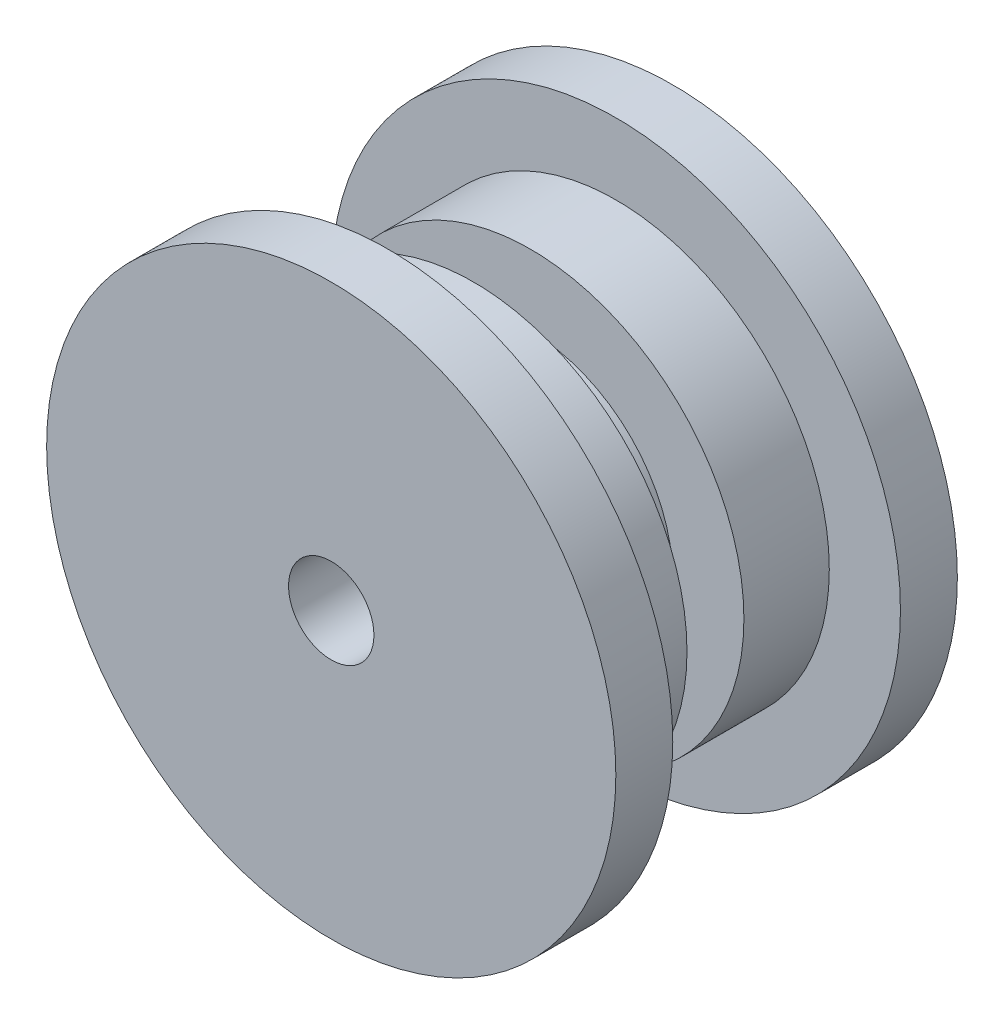
SolidWorks part; units mm, degrees
ref_plane "前视基准面" through (0, 0, 0) normal (0, 0, 1) x (1, 0, 0)
ref_plane "上视基准面" through (0, 0, 0) normal (0, 1, 0) x (1, 0, 0)
ref_plane "右视基准面" through (0, 0, 0) normal (1, 0, 0) x (0, 0, -1)
other "Configuration Table"
sketch "草图1" plane through (0, 0, 0) normal (0, 0, 1) x (1, 0, 0)
  circle A0 centre (0, 0) radius 10
  dimension "D1" = 20
extrude "凸台-拉伸1" add sketch "草图1" along normal blind 2
sketch "草图2" plane through (0, 0, 2) normal (0, 0, 1) x (1, 0, 0)
  circle A0 centre (0, 0) radius 7.5
  dimension "D1" = 15
extrude "凸台-拉伸2" add sketch "草图2" along normal blind 3
sketch "草图3" plane through (0, 0, 5) normal (0, 0, 1) x (1, 0, 0)
  circle A0 centre (0, 0) radius 5
  dimension "D1" = 10
extrude "凸台-拉伸3" add sketch "草图3" along normal blind 2
sketch "草图4" plane through (0, 0, 7) normal (0, 0, 1) x (1, 0, 0)
  circle A0 centre (0, 0) radius 7.5 construction
  circle A1 centre (0, 0) radius 7.5
extrude "凸台-拉伸4" add sketch "草图4" along normal blind 3
sketch "草图5" plane through (0, 0, 10) normal (0, 0, 1) x (1, 0, 0)
  circle A0 centre (0, 0) radius 10 construction
  circle A1 centre (0, 0) radius 10
extrude "凸台-拉伸5" add sketch "草图5" along normal blind 2
sketch "草图6" plane through (0, 0, 0) normal (0, 0, -1) x (-1, 0, 0)
  circle A0 centre (0, 0) radius 1.5
  dimension "D1" = 3
extrude "切除-拉伸1" cut sketch "草图6" against normal blind 22
